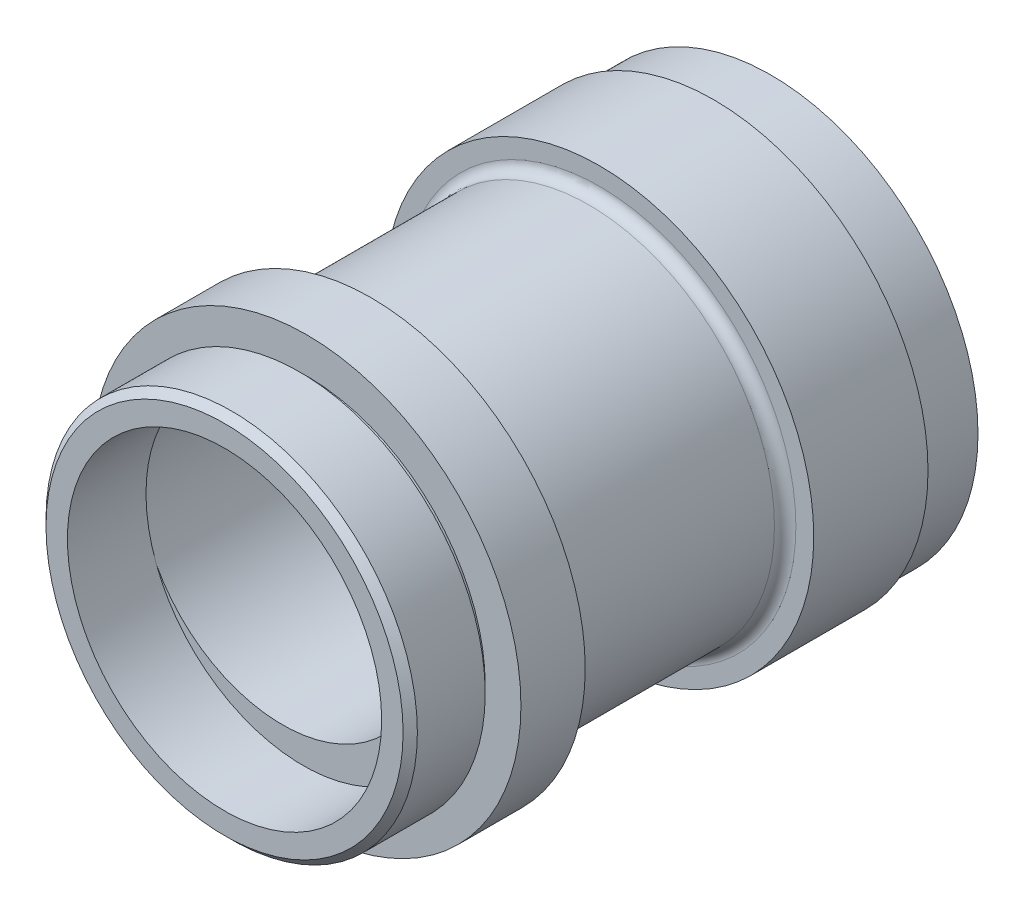
SolidWorks part; units mm, degrees
material "Copper"
ref_plane "Plan de face" through (0, 0, 0) normal (0, 0, 1) x (1, 0, 0)
ref_plane "Plan de dessus" through (0, 0, 0) normal (0, 1, 0) x (1, 0, 0)
ref_plane "Plan de droite" through (0, 0, 0) normal (1, 0, 0) x (0, 0, -1)
sketch "Sketch1" plane through (0, 0, 0) normal (0, 0, 1) x (1, 0, 0)
  circle A0 centre (0, 0) radius 14.5
  dimension "D1" = 29
extrude "Boss-Extrude1" add sketch "Sketch1" along normal blind 4
sketch "Sketch2" plane through (0, 0, 4) normal (0, 0, 1) x (1, 0, 0)
  circle A0 centre (0, 0) radius 15
  dimension "D1" = 30
extrude "Boss-Extrude2" add sketch "Sketch2" along normal blind 8
sketch "Sketch3" plane through (0, 0, 12) normal (0, 0, 1) x (1, 0, 0)
  circle A0 centre (0, 0) radius 13
  dimension "D1" = 26
extrude "Boss-Extrude3" add sketch "Sketch3" along normal blind 16
sketch "Sketch4" plane through (0, 0, 28) normal (0, 0, 1) x (1, 0, 0)
  circle A0 centre (0, 0) radius 15
  dimension "D1" = 30
extrude "Boss-Extrude4" add sketch "Sketch4" along normal blind 4.5
sketch "Sketch5" plane through (0, 0, 32.5) normal (0, 0, 1) x (1, 0, 0)
  circle A0 centre (0, 0) radius 12.5
  dimension "D1" = 25
extrude "Boss-Extrude5" add sketch "Sketch5" along normal blind 0.5
sketch "Sketch6" plane through (0, 0, 33) normal (0, 0, 1) x (1, 0, 0)
  circle A0 centre (0, 0) radius 13
  dimension "D1" = 26
extrude "Boss-Extrude6" add sketch "Sketch6" along normal blind 5.25
cosmetic thread "Cosmetic Thread1" parameters "D2"=25
sketch "Sketch7" plane through (0, 0, 38.25) normal (0, 0, 1) x (1, 0, 0)
  circle A0 centre (0, 0) radius 11
  dimension "D1" = 22
extrude "Cut-Extrude1" cut sketch "Sketch7" against normal blind 5.5
sketch "Sketch8" plane through (0, 0, 32.75) normal (0, 0, 1) x (1, 0, 0)
  circle A0 centre (-1.44, 0.75) radius 10
  circle A1 centre (0, 0) radius 15 construction
  dimension "D1" = 20
  dimension "D2" = 0.75
  dimension "D3" = 1.44
other "AlignGroup1"
extrude "Cut-Extrude2" cut sketch "Sketch8" against normal blind 32.75 contours A0
fillet "Fillet1" radius 0.75 2 edges at (13, 0, 12) (13, 0, 28)
chamfer "Chamfer1" distance 0.5 angle 45 1 edges at (13, 0, 38.25)
sketch "Sketch14" plane through (0, 0, 0) normal (0, 0, -1) x (-1, 0, 0)
  circle A0 centre (-9.5, 8.9) radius 1
  point P0 (-9.5, 8.9)
  dimension "D1" = 9.5
  dimension "D4" = 2
  dimension "D2" = 8.9
hole_wizard "Ø2.0 (2) Diameter Hole3" positions "Sketch14" profile "Sketch15" hole size "Ø2.0" standard "ISO"
sketch "Sketch15" plane through (9.5, 8.9, 0) normal (1, 0, 0) x (0, 1, 0)
  line L0 (0, 0) -> (0, 9.8509)
  line L1 (0, 9.8509) -> (1, 9.25)
  line L2 (1, 9.25) -> (1, 0)
  line L5 (1, 0) -> (0, 0)
  line L10 (0, 9.8509) -> (-1, 9.25) construction
  line L11 (0, -6.35) -> (0, 107.95) construction
  dimension "Hole Dia." = 2
  dimension "Hole Depth" = 9.25
  dimension "Drill Angle" = 118
sketch "Sketch16" plane through (0, 0, 0) normal (0, 0, -1) x (-1, 0, 0)
  line L0 (0, 0) -> (-9.5, 8.9) construction
  line L1 (0, 0) -> (9.9134, 10.5818) construction
  circle A0 centre (0, 0) radius 14.5 construction
ref_plane "Plane1" through (0, 0, 0) normal (0.7298, 0.6837, 0) x (0, 0, -1)
sketch "Sketch17" plane through (0, 0, 0) normal (0.7298, 0.6837, 0) x (0, 0, -1)
  line L0 (0, 0) -> (-20, 0) construction
  circle A0 centre (-20, 0) radius 1
  dimension "D2" = 2
  dimension "D1" = 20
extrude "Cut-Extrude3" cut sketch "Sketch17" against normal up to next
sketch "Sketch18" plane through (0, 0, 0) normal (0.7298, 0.6837, 0) x (0, 0, -1)
  line L0 (0, 0) -> (-9, 0) construction
  circle A0 centre (-9, 0) radius 1
  dimension "D2" = 2
  dimension "D1" = 9
extrude "Cut-Extrude4" cut sketch "Sketch18" along normal blind 13
